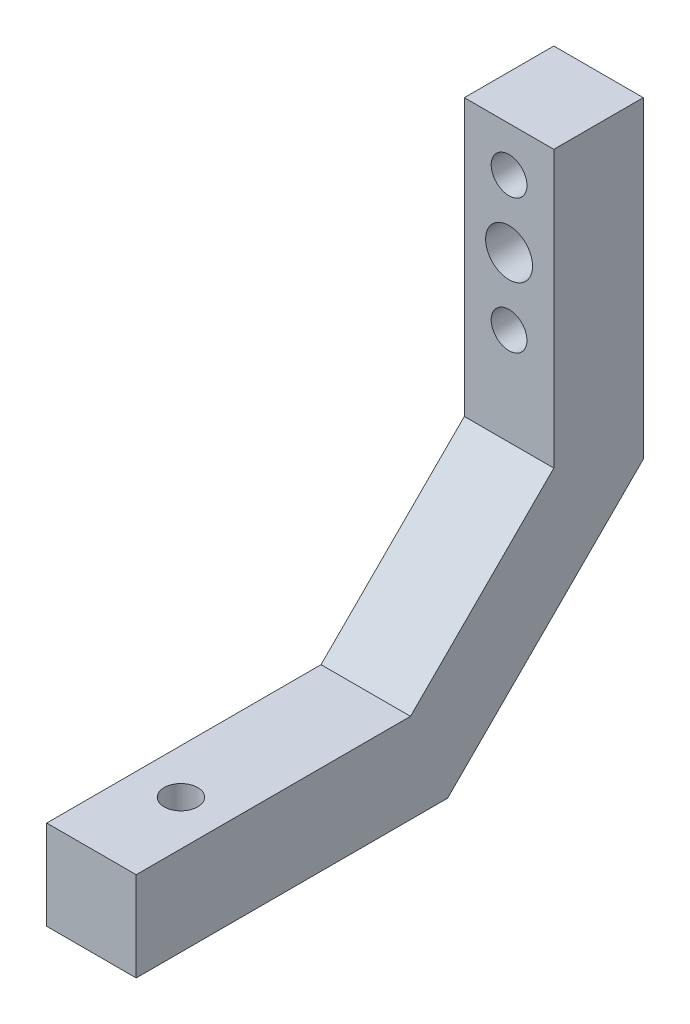
SolidWorks part; units mm, degrees
ref_plane "Front Plane" through (0, 0, 0) normal (0, 0, 1) x (1, 0, 0)
ref_plane "Top Plane" through (0, 0, 0) normal (0, 1, 0) x (1, 0, 0)
ref_plane "Right Plane" through (0, 0, 0) normal (1, 0, 0) x (0, 0, -1)
ref_axis "Z" through (0, 0, 47.607) along (0, 0, -1)
sketch "Sketch1" plane through (0, 0, 0) normal (1, 0, 0) x (0, 0, -1)
  line L0 (-8, 10) -> (0, 10)
  line L1 (0, 10) -> (0, -18)
  line L2 (0, -18) -> (-17.5, -35.5)
  line L3 (-17.5, -35.5) -> (-37.34, -35.5)
  line L4 (-37.34, -35.5) -> (-37.34, -27.5) construction
  line L5 (-37.34, -27.5) -> (-20.8137, -27.5)
  line L6 (-20.8137, -27.5) -> (-8, -14.6863)
  line L7 (-8, -14.6863) -> (-8, 10)
  line L8 (-13.4134, -20.0997) -> (-7.7566, -25.7566) construction
  line L10 (-37.34, -27.5) -> (-45.34, -27.5)
  line L11 (-37.34, -27.5) -> (-37.34, -35.5) construction
  line L12 (-37.34, -35.5) -> (-45.34, -35.5)
  line L13 (-45.34, -27.5) -> (-45.34, -35.5)
  dimension "D1" = 8
  dimension "D2" = 37.34
  dimension "D3" = 35.5
  dimension "D4" = 10
  dimension "D5" = 135
  dimension "D6" = 17.5
  dimension "D7" = 8
extrude "Boss-Extrude1" add sketch "Sketch1" along normal blind 4 and the other way blind 4
sketch "Sketch3" plane through (0, -27.5, 0) normal (0, 1, 0) x (1, 0, 0)
  line L0 (-55, 0) -> (55, 0) construction
  line L1 (0, -55) -> (0, 55) construction
  circle A0 centre (0, -37.34) radius 1.5
  dimension "D2" = 3
  dimension "D1" = 37.34
extrude "Cut-Extrude1" cut sketch "Sketch3" against normal through all
sketch "Sketch4" plane through (0, 0, 8) normal (0, 0, 1) x (1, 0, 0)
  line L0 (0, -6) -> (0, 6) construction
  circle A0 centre (0, 0) radius 2.1
  circle A1 centre (0, 6) radius 1.6
  circle A2 centre (0, -6) radius 1.6
  dimension "D1" = 4.2
  dimension "D3" = 3.2
  dimension "D2" = 12
extrude "Cut-Extrude2" cut sketch "Sketch4" against normal through all
ref_axis "Axis1" through (0, -27.5, 37.34) along (0, 1, 0)
equation "\"rbracket-width\"= 8"
equation "\"D1@Boss-Extrude1\"=\"rbracket-width\"/2"
equation "\"D2@Boss-Extrude1\"=\"rbracket-width\"/2"
equation "\"EyeCaptureRadius\"= ( \"EyeDiameter\" + \"EyeClearance\" ) / 2"
equation "\"rbracket_planetocenterline_dist\"= \"BasePlaneDistance\""
equation "\"D2@Sketch1\"=\"rbracket_planetocenterline_dist\""
equation "\"EyeDiameter\" = 35"
equation "\"BasePlaneDistance\" = \"EyeDiameter\"/2+19.84"
equation "\"EyeClearance\" = 2"
equation "\"D1@Sketch1\"=\"rbracket-width\""
equation "\"D3@Sketch1\"=(\"EyeDiameter\"+\"EyeClearance\"+\"EyeClearance\")/2 + \"L2Thickness\" + \"rbracket-width\""
equation "\"D4@Sketch1\"= 10"
equation "\"D6@Sketch1\"=\"EyeDiameter\"/2"
equation "\"D7@Sketch1\"=\"rbracket-width\""
equation "\"D1@Sketch3\"=\"BasePlaneDistance\""
equation "\"L2Thickness\" = 8"
